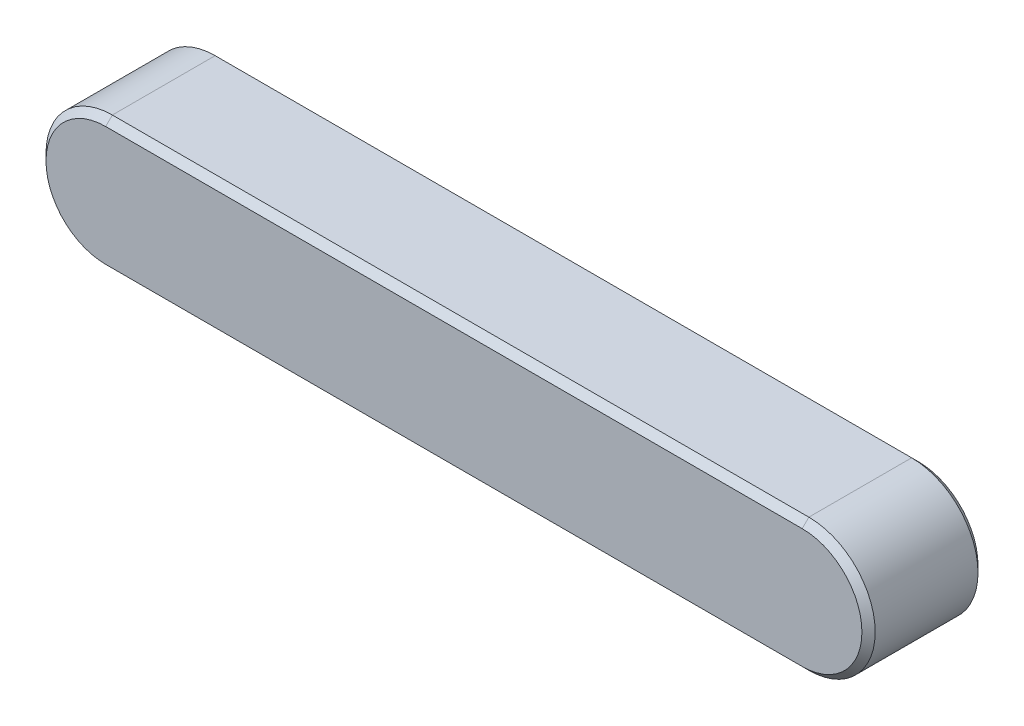
SolidWorks part; units mm, degrees
ref_plane "Front" through (0, 0, 0) normal (0, 0, 1) x (1, 0, 0)
ref_plane "Top" through (0, 0, 0) normal (0, 1, 0) x (1, 0, 0)
ref_plane "Right" through (0, 0, 0) normal (1, 0, 0) x (0, 0, -1)
sketch "body" plane through (0, 0, 0) normal (0, 0, 1) x (1, 0, 0)
  line L0 (42, 8) -> (-18, 8)
  line L1 (42, 0) -> (-18, 0)
  arc A0 (42, 8) -> (42, 0) centre (42, 4) cw
  arc A1 (0, 8) -> (0, 0) centre (0, 4) ccw
  circle A2 centre (0, 4) radius 4 construction
  point P7 (-4, 4)
  dimension "D1" = 60
  dimension "Length" = 50
extrude "Extrude1" add sketch "body" along normal blind 7 contours L0 A1 L1 A0 region at (21, 4, 0)
chamfer "Chamfer1" distance 0.4 8 edges at (-4, 4, 0) (21, 0, 0) (46, 4, 0) (21, 8, 0) (46, 4, 7) (21, 0, 7) (-4, 4, 7) (21, 8, 7)
equation "\"D1@body\" = \"Length@body\" + 10"
